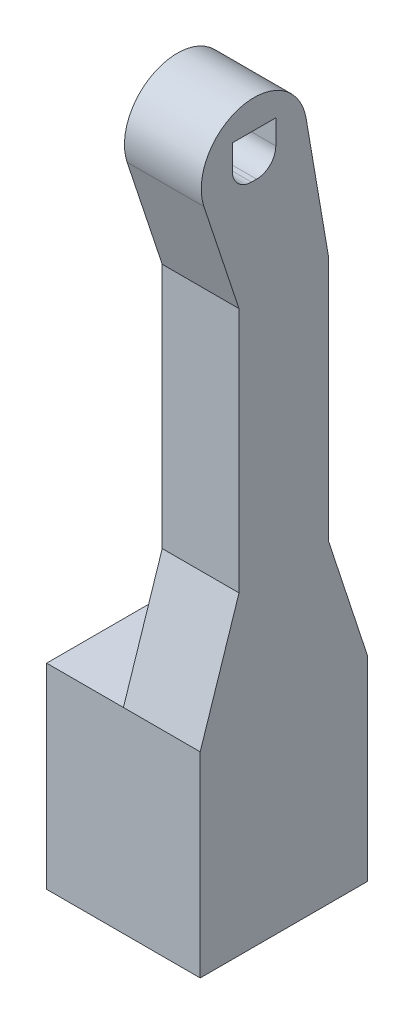
SolidWorks part; units mm, degrees
ref_plane "Front Plane" through (0, 0, 0) normal (0, 0, 1) x (1, 0, 0)
ref_plane "Top Plane" through (0, 0, 0) normal (0, 1, 0) x (1, 0, 0)
ref_plane "Right Plane" through (0, 0, 0) normal (1, 0, 0) x (0, 0, -1)
sketch "Sketch1" plane through (0, 0, 0) normal (1, 0, 0) x (0, 0, -1)
  line L0 (-3, 9.82) -> (-3, 0)
  line L1 (-3, 0) -> (-6.5301, 0)
  line L2 (-6.5301, 0) -> (-6.5301, 9.82)
  line L3 (-6.5301, 15.3053) -> (-3.4983, 24.5417)
  line L4 (-3.4983, 24.5417) -> (-3.4983, 43.7787)
  line L5 (0, 0) -> (0, 50000) construction
  line L6 (3.4983, 24.5417) -> (3.4983, 43.7787)
  line L7 (6.5301, 15.3053) -> (3.4983, 24.5417)
  line L8 (6.5301, 0) -> (6.5301, 9.82)
  line L9 (3, 0) -> (6.5301, 0)
  line L10 (3, 9.82) -> (3, 0)
  line L11 (-3, 9.82) -> (3, 9.82)
  line L12 (-2.5244, 52.0529) -> (-2.1244, 52.0529) construction
  line L13 (-2.5244, 53.3529) -> (-2.1244, 53.3529) construction
  line L14 (-3.8244, 55.0529) -> (-3.8244, 53.3529) construction
  line L15 (-0.8244, 53.3529) -> (-0.8244, 55.0529) construction
  line L16 (-0.8244, 55.0529) -> (-3.8244, 55.0529) construction
  line L17 (-3.8244, 55.0529) -> (-0.8244, 55.0529) construction
  line L18 (-2.5244, 52.0529) -> (-2.1244, 52.0529) construction
  line L19 (-3.8244, 55.0529) -> (-3.8244, 53.3529) construction
  line L20 (-0.8244, 53.3529) -> (-0.8244, 55.0529) construction
  line L21 (-0.8244, 55.0529) -> (-3.8244, 55.0529) construction
  line L22 (-3.8244, 55.0529) -> (-0.8244, 55.0529)
  line L23 (-3.4983, 43.7787) -> (-6.2409, 52.0551)
  line L24 (3.4983, 43.7787) -> (1.7425, 54.0483)
  line L25 (6.5301, 9.82) -> (6.5301, 15.3053)
  line L26 (-6.5301, 9.82) -> (-6.5301, 15.3053)
  line L27 (-6.5301, 9.82) -> (-3, 9.82)
  line L28 (3, 9.82) -> (6.5301, 9.82)
  line L29 (3, 0) -> (-3, 0)
  line L30 (6.5301, 15.3053) -> (-6.5301, 15.3053)
  line L31 (-0.6244, 55.2529) -> (-4.0244, 55.2529)
  line L32 (-4.0244, 55.2529) -> (-4.0244, 53.3529)
  line L33 (-2.5244, 51.8529) -> (-2.1244, 51.8529)
  line L34 (-0.6244, 53.3529) -> (-0.6244, 55.2529)
  arc A0 (-2.1244, 52.0529) -> (-0.8244, 53.3529) centre (-2.1244, 53.3529) ccw construction
  arc A1 (-3.8244, 53.3529) -> (-2.5244, 52.0529) centre (-2.5244, 53.3529) ccw construction
  arc A2 (-2.1244, 52.0529) -> (-0.8244, 53.3529) centre (-2.1244, 53.3529) ccw construction
  arc A3 (-3.8244, 53.3529) -> (-2.5244, 52.0529) centre (-2.5244, 53.3529) ccw construction
  arc A4 (-6.2409, 52.0551) -> (1.7425, 54.0483) centre (-2.3244, 53.3529) cw
  arc A5 (-4.0244, 53.3529) -> (-2.5244, 51.8529) centre (-2.5244, 53.3529) ccw
  arc A6 (-2.1244, 51.8529) -> (-0.6244, 53.3529) centre (-2.1244, 53.3529) ccw
  dimension "D3" = 0.2
  dimension "D1" = 6
  dimension "D2" = 9.82
extrude "Boss-Extrude2" add sketch "Sketch1" against normal blind 6 contours L28 L10 L9 L8 | L27 L2 L1 L0 | L25 L30 L26 L27 L11 L28 region at (0, 12.5626, 0) region at (0, 4.91, 4.7651) region at (0, 4.91, -4.7651)
extrude "Boss-Extrude3" add sketch "Sketch1<4>" along normal blind 6 contours L29 L10 L11 L0 | L27 L2 L1 L0 | L28 L10 L9 L8 | L25 L30 L26 L27 L11 L28 | A4 L23 L4 L3 L30 L7 L6 L24 A3 L19 L21 L20 A2 L18 region at (0, 4.91, 0) region at (0, 12.5626, 0) region at (0, 4.91, 4.7651) region at (0, 4.91, -4.7651) region at (0, 34.3885, 0.4068)
sketch "Sketch1<4>" plane through (0, 0, 0) normal (1, 0, 0) x (0, 0, -1) same geometry as "Sketch1"
